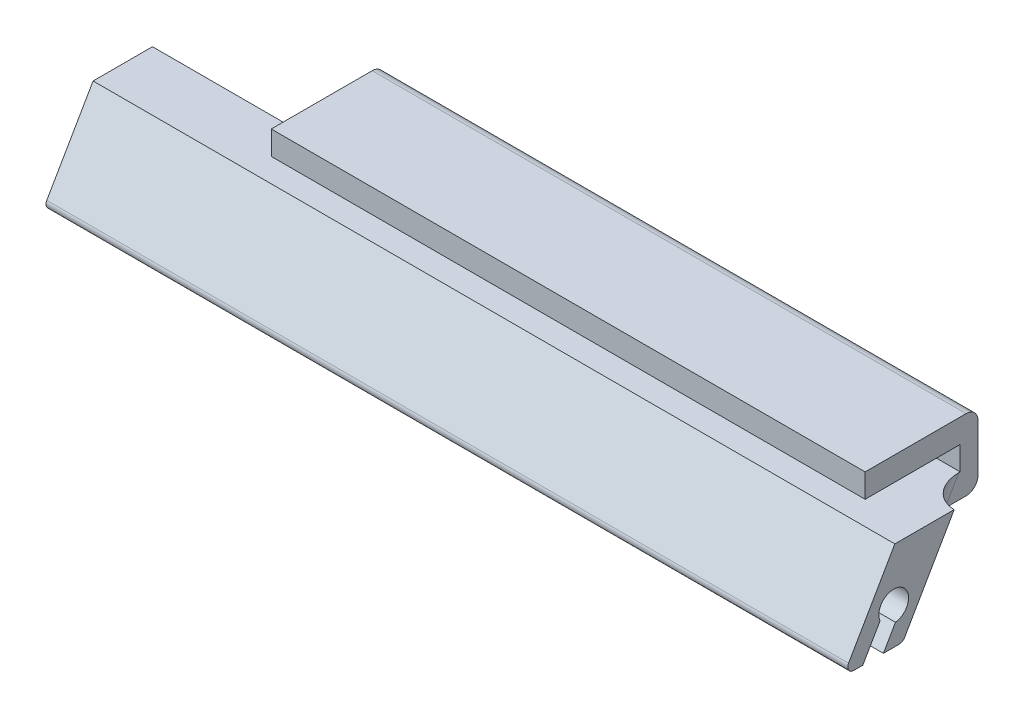
SolidWorks part; units mm, degrees
ref_plane "Front Plane" through (0, 0, 0) normal (0, 0, 1) x (1, 0, 0)
ref_plane "Top Plane" through (0, 0, 0) normal (0, 1, 0) x (1, 0, 0)
ref_plane "Right Plane" through (0, 0, 0) normal (1, 0, 0) x (0, 0, -1)
sketch "Sketch2" plane through (0, 0, 0) normal (1, 0, 0) x (0, 0, -1)
  line L0 (0, 0) -> (8.6603, 15)
  line L1 (8.6603, 15) -> (18.6603, 15)
  line L2 (18.6603, 15) -> (10, 0)
  line L3 (10, 0) -> (0, 0)
  line L4 (0, 0) -> (0, 15) construction
  line L5 (13.6603, 15) -> (5, 0) construction
  line L6 (3.2679, 0) -> (7.1651, 6.75)
  line L7 (7.1651, 6.75) -> (9.7631, 5.25)
  line L8 (9.7631, 5.25) -> (6.7321, 0)
  line L34 (8.6603, 15) -> (27.6603, 15)
  line L35 (8.6603, 15) -> (8.6603, 11)
  line L36 (8.6603, 11) -> (27.6603, 11)
  line L37 (27.6603, 15) -> (27.6603, 11)
  line L38 (27.6603, 15) -> (24.6603, 15)
  line L39 (27.6603, 15) -> (27.6603, 19)
  line L40 (27.6603, 19) -> (24.6603, 19)
  line L41 (24.6603, 15) -> (24.6603, 19)
  line L42 (27.6603, 19) -> (8.6603, 19)
  line L43 (27.6603, 19) -> (27.6603, 23)
  line L44 (27.6603, 23) -> (8.6603, 23)
  line L45 (8.6603, 19) -> (8.6603, 23)
  circle A0 centre (8.4641, 6) radius 2.5
  point P14 (8.4641, 6)
  dimension "D5" = 5
  dimension "D1" = 30
  dimension "D2" = 10
  dimension "D3" = 15
  dimension "D4" = 3
  dimension "D6" = 6
  dimension "D7" = 4
  dimension "D8" = 4
  dimension "D9" = 3
  dimension "D10" = 6
extrude "Boss-Extrude2" add sketch "Sketch2" along normal blind 100 contours L45 L42 L40 L43 L44 | L41 L34 L39 L40 | L37 L34 L2 L36 | L35 L36 L2 L1 | A0 L8 L3 L2 L36 L35 L0 L6 region at (0, 7.3891, -4.5223) region at (0, 13.087, -13.108) region at (0, 12.9242, -22.561) region at (0, 17, -26.1603) region at (0, 21, -18.1603)
sketch "Sketch3" plane through (100, 0, 0) normal (1, 0, 0) x (0, 0, -1)
  line L0 (0, 0) -> (8.6603, 15)
  line L2 (8.6603, 15) -> (18.6603, 15)
  line L3 (18.6603, 15) -> (10, 0)
  line L4 (10, 0) -> (6.7321, 0)
  line L5 (6.7321, 0) -> (8.7631, 3.5179)
  line L6 (8.7631, 3.5179) -> (6.1651, 5.0179)
  line L7 (6.1651, 5.0179) -> (3.2679, 0)
  line L8 (3.2679, 0) -> (0, 0)
  line L9 (8.6603, 15) -> (24.6603, 15) construction
  line L10 (0, 0) -> (8.6603, 15) construction
  circle A0 centre (8.4641, 6) radius 2.5
  arc A1 (8.7631, 3.5179) -> (6.1651, 5.0179) centre (8.4641, 6) ccw construction
  point P3 (8.6603, 15)
  point P22 (0, 0)
  line M14 (8.6603, 15) -> (0, 0)
  line M15 (0, 0) -> (3.2679, 0)
  line M16 (3.2679, 0) -> (6.1651, 5.0179)
  arc M17 (6.1651, 5.0179) -> (8.7631, 3.5179) centre (8.4641, 6) cw
  line M18 (8.7631, 3.5179) -> (6.7321, 0)
  line M19 (6.7321, 0) -> (10, 0)
  line M20 (10, 0) -> (16.3509, 11)
extrude "Boss-Extrude3" add sketch "Sketch3" along normal blind 5 and the other way blind 130 contours L2 M14 M15 M16 M17 M18 M19 M20 region at (100, 8.4003, -9.8628)
fillet "Fillet5" radius 10 1 edges at (50, 11, -16.3509)
fillet "Fillet6" radius 5 2 edges at (0, 10.5, -16.0622) (100, 10.5, -16.0622)
fillet "Fillet7" radius 2 2 edges at (50, 11, -27.6603) (50, 23, -27.6603)
fillet "Fillet8" radius 1 2 edges at (37.5, 0, -10) (37.5, 0, 0)
